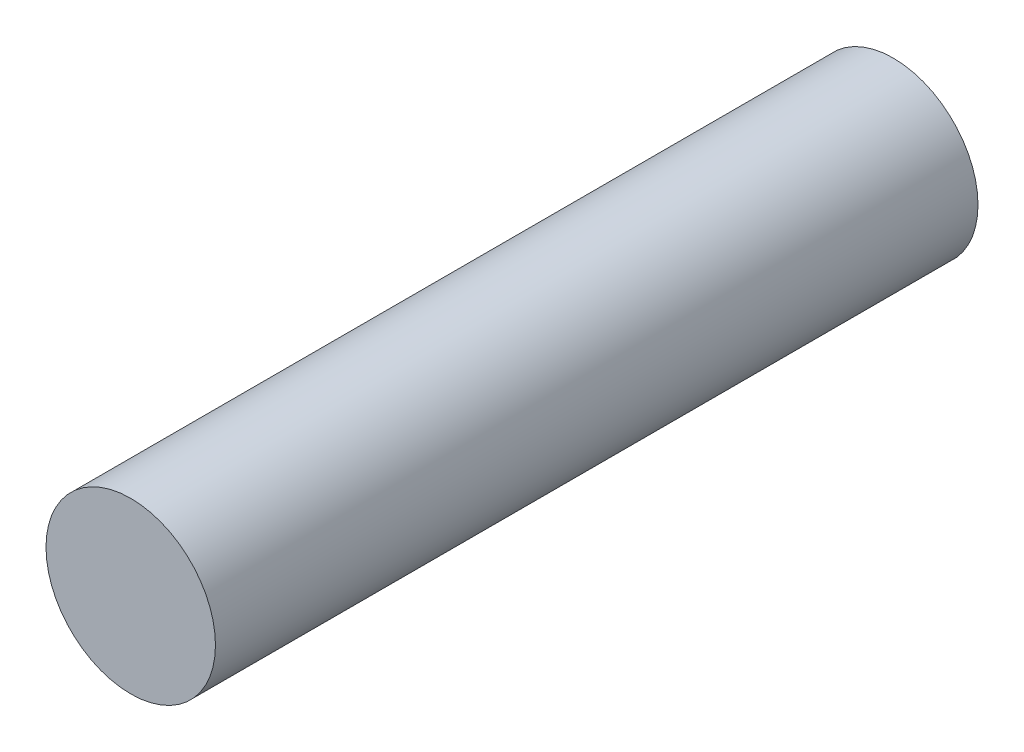
SolidWorks part; units mm, degrees
ref_plane "Front Plane" through (0, 0, 0) normal (0, 0, 1) x (1, 0, 0)
ref_plane "Top Plane" through (0, 0, 0) normal (0, 1, 0) x (1, 0, 0)
ref_plane "Right Plane" through (0, 0, 0) normal (1, 0, 0) x (0, 0, -1)
sketch "Sketch2" plane through (0, 0, 0) normal (0, 0, 1) x (1, 0, 0)
  circle A0 centre (0, 0) radius 30
  dimension "D1" = 60
extrude "Boss-Extrude1" add sketch "Sketch2" along normal blind 270
ref_plane "Plane1" through (0, 0, 135) normal (0, 0, 1) x (1, 0, 0)
ref_axis "Axis1" through (0, 0, 270) along (0, 0, -1)
